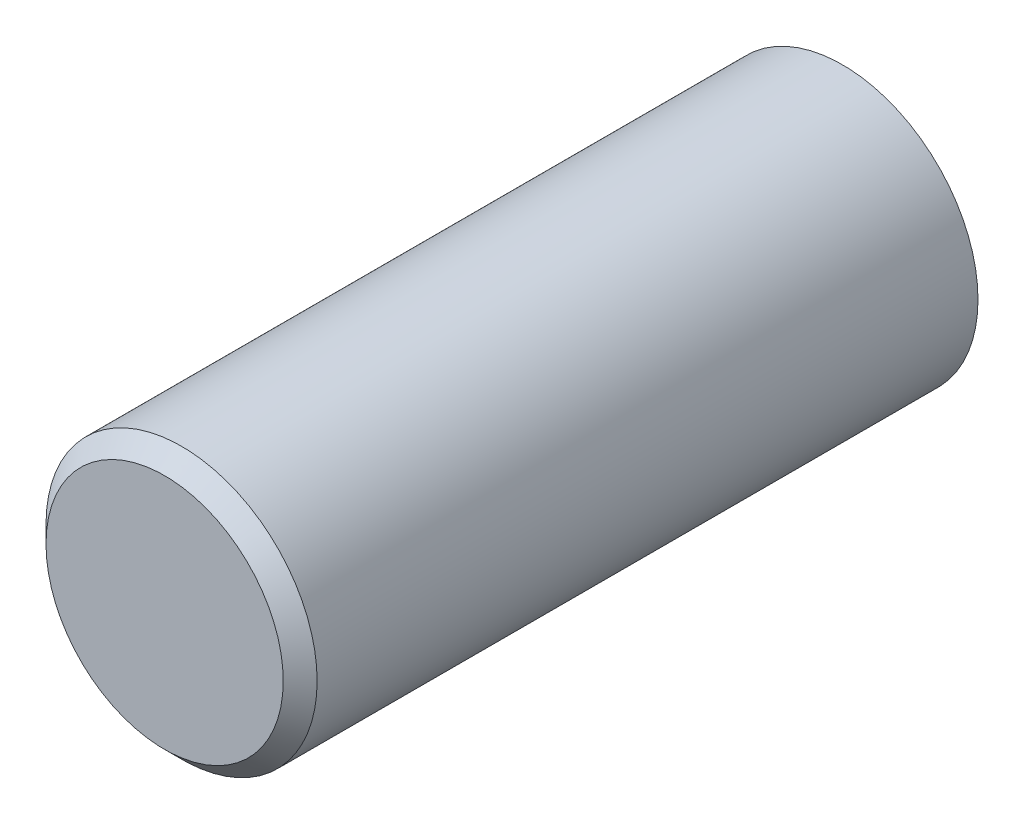
SolidWorks part; units mm, degrees
ref_plane "Front" through (0, 0, 0) normal (0, 0, 1) x (1, 0, 0)
ref_plane "Top" through (0, 0, 0) normal (0, 1, 0) x (1, 0, 0)
ref_plane "Right" through (0, 0, 0) normal (1, 0, 0) x (0, 0, -1)
sketch "Esquisse1" plane through (0, 0, 0) normal (0, 0, 1) x (1, 0, 0)
  circle A0 centre (0, 0) radius 4
  dimension "D1" = 8
extrude "Boss.-Extru.1" add sketch "Esquisse1" along normal blind 20
chamfer "Chanfrein1" distance 0.5 angle 45 1 edges at (4, 0, 20)
